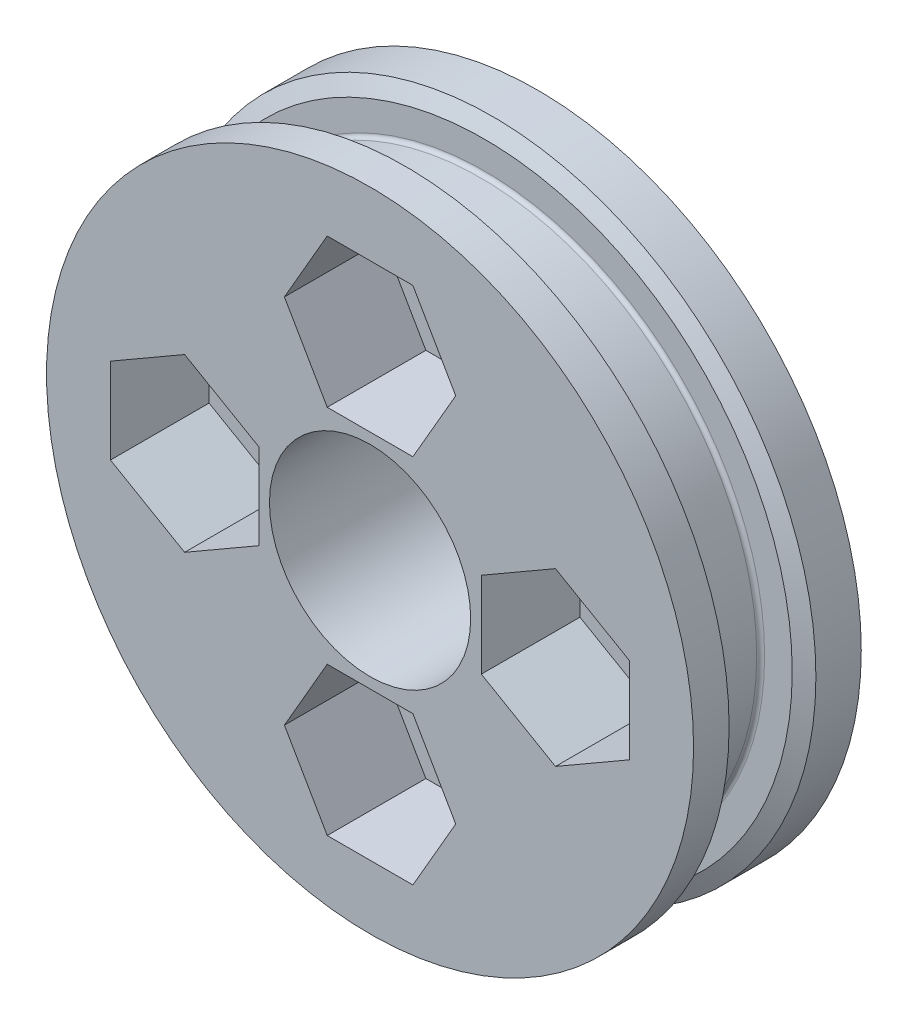
SolidWorks part; units mm, degrees
material "1060 Alloy"
ref_plane "Front Plane" through (0, 0, 0) normal (0, 0, 1) x (1, 0, 0)
ref_plane "Top Plane" through (0, 0, 0) normal (0, 1, 0) x (1, 0, 0)
ref_plane "Right Plane" through (0, 0, 0) normal (1, 0, 0) x (0, 0, -1)
sketch "Sketch2" plane through (0, 0, 0) normal (1, 0, 0) x (0, 0, -1)
  line L0 (0, 6.477) -> (0, 20.828)
  line L1 (0, 20.828) -> (2.286, 20.828)
  line L2 (2.794, 19.812) -> (2.794, 17.78)
  line L3 (2.794, 17.78) -> (7.366, 17.78)
  line L4 (7.366, 17.78) -> (7.366, 19.812)
  line L5 (7.874, 20.828) -> (10.795, 20.828)
  line L6 (10.795, 20.828) -> (10.795, 6.477)
  line L8 (0, 6.477) -> (10.795, 6.477)
  line L9 (0, 6.477) -> (0, 0) construction
  line L10 (0, 0) -> (10.7816, 0) construction
  line L11 (7.366, 19.812) -> (7.874, 20.828)
  line L12 (2.286, 20.828) -> (2.794, 19.812)
  point P4 (2.794, 20.828)
  point P7 (7.366, 20.828)
  dimension "D1" = 17.78
  dimension "D2" = 10.795
  dimension "D3" = 3.048
  dimension "D4" = 6.477
  dimension "D5" = 4.572
  dimension "D6" = 1.016
  dimension "D7" = 0.508
  dimension "D8" = 0.508
  dimension "D9" = 1.016
  dimension "D10" = 2.921
revolve "Revolve1" add sketch "Sketch2" angle 360 about L10
sketch "Sketch3" plane through (0, 0, -10.795) normal (0, 0, -1) x (-1, 0, 0)
  line L1 (-8.255, -8.255) -> (8.255, -8.255)
  line L2 (-8.255, -8.255) -> (-8.255, 8.255)
  line L3 (-8.255, 8.255) -> (8.255, 8.255)
  line L4 (8.255, -8.255) -> (8.255, 8.255)
  circle A0 centre (0, 0) radius 6.477 construction
  circle A1 centre (0, 0) radius 6.477
  point P4 (8.255, 0)
  point P6 (0, 8.255)
  dimension "D1" = 16.51
extrude "Boss-Extrude1" add sketch "Sketch3" along normal blind 3.175
ref_plane "Plane1" through (0, 0, -5.3975) normal (0, 0, -1) x (-1, 0, 0)
sketch "Sketch4" plane through (0, 0, -10.795) normal (0, 0, -1) x (-1, 0, 0)
  line L0 (0, 11.938) -> (0, 0) construction
  line L1 (0, 0) -> (0, -11.938) construction
  line L2 (-11.938, 0) -> (0, 0) construction
  line L3 (0, 0) -> (11.938, 0) construction
  circle A0 centre (0, 11.938) radius 2.54
  circle A1 centre (11.938, 0) radius 2.54
  circle A2 centre (0, -11.938) radius 2.54
  circle A3 centre (-11.938, 0) radius 2.54
  dimension "D1" = 5.08
  dimension "D2" = 11.938
extrude "Cut-Extrude1" cut sketch "Sketch4" against normal through all both and the other way through all
fillet "Fillet1" radius 0.254 2 edges at (17.78, 0, -7.366) (17.78, 0, -2.794)
sketch "Sketch5" plane through (0, 0, 0) normal (0, 0, 1) x (1, 0, 0)
  line L1 (2.757, 7.1628) -> (5.5139, 11.938)
  line L2 (5.5139, 11.938) -> (2.757, 16.7132)
  line L3 (2.757, 16.7132) -> (-2.757, 16.7132)
  line L4 (-2.757, 16.7132) -> (-5.5139, 11.938)
  line L5 (-5.5139, 11.938) -> (-2.757, 7.1628)
  line L6 (-2.757, 7.1628) -> (2.757, 7.1628)
  circle A0 centre (0, 11.938) radius 4.7752 construction
  circle A1 centre (0, 11.938) radius 2.54 construction
  dimension "D1" = 9.5504
extrude "Cut-Extrude2" cut sketch "Sketch5" against normal blind 6.35
pattern_circular "CirPattern1" count 4 over 360 about axis through (0, 0, 0) along (0, 0, 1) of "Cut-Extrude2"
